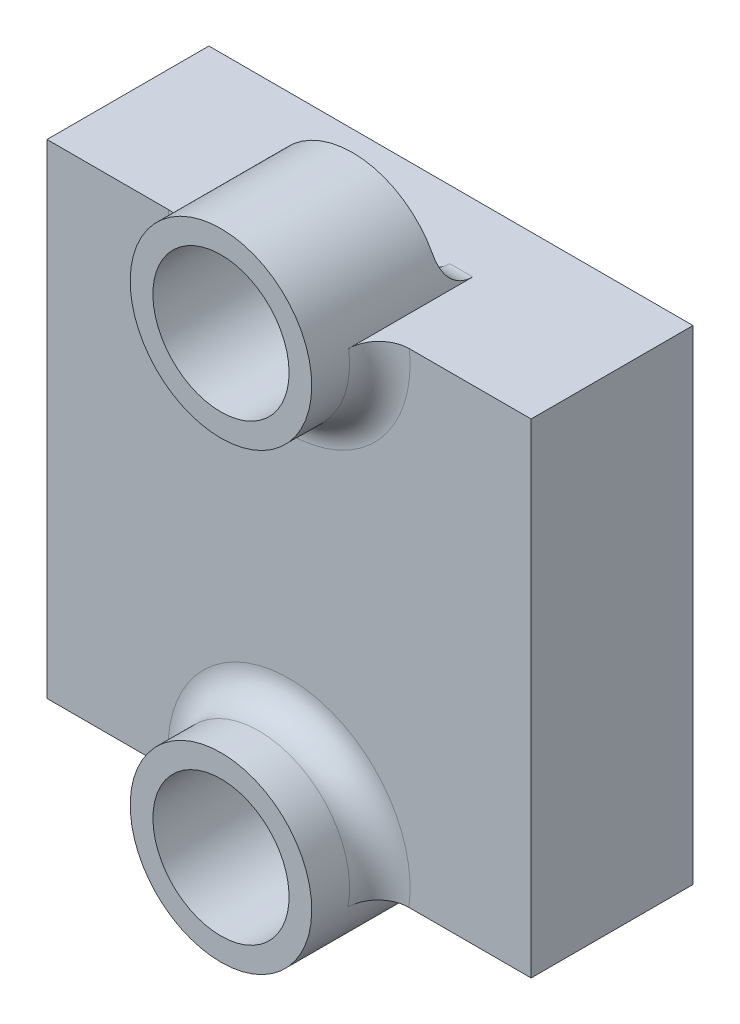
SolidWorks part; units mm, degrees
note: The reader was unsure of these and kept them because the rebuilt part matched: shared geometry of "Sketch5<4>", "Sketch5<5>", "Sketch5<6>".
material "ABS"
ref_plane "Front Plane" through (0, 0, 0) normal (0, 0, 1) x (1, 0, 0)
ref_plane "Top Plane" through (0, 0, 0) normal (0, 1, 0) x (1, 0, 0)
ref_plane "Right Plane" through (0, 0, 0) normal (1, 0, 0) x (0, 0, -1)
sketch "Sketch5" plane through (0, 0, 9.6) normal (0, 0, 1) x (1, 0, 0)
  line L0 (-72, -8) -> (-56, -8)
  line L1 (-72, -8) -> (-72, -24)
  line L2 (-56, -8) -> (-56, -24)
  line L4 (-72, -24) -> (-56, -24)
  line L5 (-56, -24) -> (-56, 8)
  line L6 (-56, 8) -> (-72, 8)
  line L7 (-72, 8) -> (-72, -24)
  line L8 (-72, -24) -> (-56, -24)
  arc A0 (-65.55, -23.425) -> (-62.45, -23.425) centre (-64, -23.425) ccw construction
  arc A1 (-65.55, -8.425) -> (-62.45, -8.425) centre (-64, -8.425) ccw construction
  arc A2 (-65.55, -23.425) -> (-62.45, -23.425) centre (-64, -23.425) ccw construction
  arc A3 (-65.55, -8.425) -> (-62.45, -8.425) centre (-64, -8.425) ccw construction
  circle A4 centre (-64, -8.425) radius 2.25
  circle A5 centre (-64, -23.425) radius 2.25
  circle A12 centre (-60, -12) radius 2.4 construction
  circle A13 centre (-60, -20) radius 2.4 construction
  circle A14 centre (-68, -20) radius 2.4 construction
  circle A15 centre (-68, -12) radius 2.4 construction
  circle A16 centre (-60, -12) radius 2.4 construction
  circle A17 centre (-60, -20) radius 2.4 construction
  circle A18 centre (-68, -20) radius 2.4 construction
  circle A19 centre (-68, -12) radius 2.4 construction
  circle A24 centre (-68, -20) radius 2.55
  circle A25 centre (-68, -12) radius 2.55
  circle A26 centre (-60, -12) radius 2.55
  circle A27 centre (-60, -20) radius 2.55
  circle A28 centre (-64, -8.425) radius 3
  circle A29 centre (-64, -23.425) radius 3
  line M6 (-72, -24) -> (-56, -24)
  line M7 (-56, -24) -> (-56, 8)
  line M9 (-72, 8) -> (-72, -24)
  dimension "D2" = 4.5
  dimension "D3" = 0.15
  dimension "D5" = 6
  dimension "D6" = 16
  dimension "D1" = 0
extrude "Boss-Extrude1" add sketch "Sketch5" along normal offset from surface (1.75 mm away) 0.15 contours A29 A27 L8 L0 A28 A26 A25 A24 M7 M9 M6 | A27 A29 A24 L8 A5 M6 | L8 A5 | L0 A28 A25 A26 A4 | L0 A4
extrude "Boss-Extrude2" add sketch "Sketch5<4>" along normal blind 1.5 from surface at 1.75 contours L1 L8 L2 L0 starting at face at (-60, -14.55, 11.35)
sketch "Sketch5<4>" plane through (0, 0, 9.6) normal (0, 0, 1) x (1, 0, 0) same geometry as "Sketch5"
extrude "Boss-Extrude3" add sketch "Sketch5<5>" along normal offset from surface (2.1 mm away) 2.25 from surface at 3.25
sketch "Sketch5<5>" plane through (0, 0, 9.6) normal (0, 0, 1) x (1, 0, 0) same geometry as "Sketch5"
extrude "Boss-Extrude4" add sketch "Sketch5<6>" along normal up to surface (2.25 mm away) from surface at 5.35 contours A28 | A4 | A5 | A29 starting at face at (-64, -10.675, 14.95)
sketch "Sketch5<6>" plane through (0, 0, 9.6) normal (0, 0, 1) x (1, 0, 0) same geometry as "Sketch5"
fillet "Fillet1" radius 1 6 edges at (-66.5896, -8, 12.85) (-61.4104, -8, 12.85) (-61.4402, -24, 12.85) (-66.5598, -24, 12.85) (-64, -11.425, 14.95) (-64, -20.425, 14.95)
